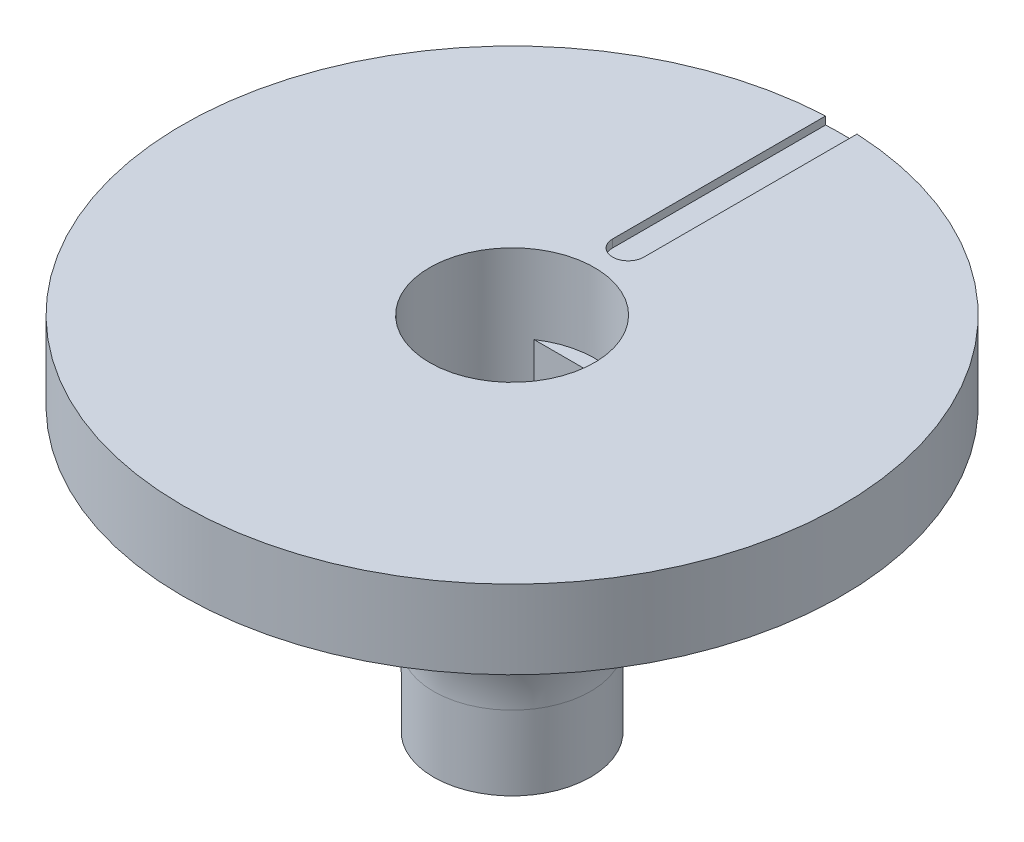
SolidWorks part; units mm, degrees
other "Markup1"
sketch "Sketch12" plane through (10.5, -11, 10.5) normal (0.0629, -0.0953, 0.9935) x (-0.9831, 0.1654, 0.0781)
material "ABS"
ref_plane "Front Plane" through (0, 0, 0) normal (0, 0, 1) x (1, 0, 0)
ref_plane "Top Plane" through (0, 0, 0) normal (0, 1, 0) x (1, 0, 0)
ref_plane "Right Plane" through (0, 0, 0) normal (1, 0, 0) x (0, 0, -1)
sketch "Sketch1" plane through (0, 0, 0) normal (0, 1, 0) x (1, 0, 0)
  circle A0 centre (0, 0) radius 8.6
  circle A1 centre (0, 0) radius 10.5
  dimension "D1" = 17.2
  dimension "D2" = 21
extrude "Boss-Extrude1" add sketch "Sketch1" against normal blind 2
ref_plane "Plane1" through (0, 0, 8.6) normal (0, 0, -1) x (-1, 0, 0)
sketch "Sketch2" plane through (0, 0, 8.6) normal (0, 0, -1) x (-1, 0, 0)
  line L0 (0.4, -1.25) -> (-0.4, -1.25)
  line L1 (0.4, -1.25) -> (0.4, 0)
  line L6 (-0.4, 0) -> (-0.4, -1.25)
  line L7 (10.5, 0) -> (-10.5, 0) construction
  line L8 (0.4, 0) -> (-0.4, 0)
  point P2 (0, -1.25)
  dimension "D1" = 1.25
  dimension "D4" = 0.8
extrude "Boss-Extrude2" add sketch "Sketch2" along normal blind 1.25
ref_plane "Plane2" through (0, 0, -8.6) normal (0, 0, 1) x (1, 0, 0)
extrude "Boss-Extrude3" add sketch "Sketch2<2>" against normal blind 1.25 from surface starting at plane "Plane2"
sketch "Sketch2<2>" plane through (0, 0, 8.6) normal (0, 0, -1) x (-1, 0, 0) same geometry as "Sketch2"
sketch "Sketch3" plane through (0, 0, 0) normal (0, 1, 0) x (1, 0, 0)
  circle A1 centre (0, 0) radius 10.5
  circle A2 centre (0, 0) radius 10.5
  dimension "D1" = 0
extrude "Boss-Extrude4" add sketch "Sketch3" along normal blind 0.5
sketch "Sketch5" plane through (0, 0, 0) normal (0, -1, 0) x (1, 0, 0)
  circle A1 centre (0, 0) radius 3.25
  dimension "D2" = 6.5
extrude "Boss-Extrude5" add sketch "Sketch5" along normal blind 6
fillet "Fillet2" radius 0.75 1 edges at (0, 0, 3.25)
sketch "Sketch4" plane through (0, 0.5, 0) normal (0, 1, 0) x (1, 0, 0)
  line L0 (-1.4697, 2.175) -> (1.4697, 2.175)
  line L1 (-3.1755, -2.625) -> (3.3726, -2.625) construction
  arc A0 (-1.4697, 2.175) -> (1.4697, 2.175) centre (0, 0) ccw
  dimension "D1" = 5.25
  dimension "D2" = 4.8
extrude "Cut-Extrude1" cut sketch "Sketch4" against normal blind 5.5
fillet "Fillet1" radius 0.25 4 edges at (-0.4, -1.25, 7.9703) (0.4, -1.25, 7.9703) (-0.4, -1.25, -7.9703) (0.4, -1.25, -7.9703)
sketch "Sketch7" plane through (0, 0.5, 0) normal (0, 1, 0) x (1, 0, 0)
  circle A2 centre (0, 0) radius 2.625
  arc A3 (-1.4697, 2.175) -> (1.4697, 2.175) centre (0, 0) ccw construction
extrude "Cut-Extrude2" cut sketch "Sketch7" against normal blind 2.5
sketch "Sketch9" plane through (0, 0.5, 0) normal (0, 1, 0) x (1, 0, 0)
  line L0 (0, 3.7) -> (0, 13.7) construction
  line L1 (-0.5, 3.7) -> (-0.5, 13.7)
  line L2 (0.5, 3.7) -> (0.5, 13.7)
  arc A0 (-0.5, 3.7) -> (0.5, 3.7) centre (0, 3.7) ccw
  arc A1 (0.5, 13.7) -> (-0.5, 13.7) centre (0, 13.7) ccw
  point P3 (0, 8.7)
  dimension "D1" = 1
  dimension "D2" = 10
  dimension "D3" = 3.7
extrude "Cut-Extrude3" cut sketch "Sketch9" against normal blind 0.25
sketch "Sketch11" plane through (0, -6, 0) normal (0, -1, 0) x (1, 0, 0)
  circle A0 centre (0, 0) radius 2.5
  dimension "D1" = 5
extrude "Boss-Extrude6" add sketch "Sketch11" along normal blind 5
sketch "Sketch10" plane through (0, -6, 0) normal (0, -1, 0) x (1, 0, 0)
  line L1 (1.8042, 0) -> (0.9021, 1.5625)
  line L2 (0.9021, 1.5625) -> (-0.9021, 1.5625)
  line L3 (-0.9021, 1.5625) -> (-1.8042, 0)
  line L4 (-1.8042, 0) -> (-0.9021, -1.5625)
  line L5 (-0.9021, -1.5625) -> (0.9021, -1.5625)
  line L6 (0.9021, -1.5625) -> (1.8042, 0)
  circle A0 centre (0, 0) radius 1.5625 construction
  dimension "D1" = 3.125
extrude "Cut-Extrude4" cut sketch "Sketch10" against normal blind 4.5 from surface starting at face at (0, -11, -2.5)
chamfer "Chamfer2" distance 0.25 angle 45 6 edges at (-1.3532, -11, 0.7813) (-1.3532, -11, -0.7813) (0, -11, -1.5625) (1.3532, -11, -0.7813) (1.3532, -11, 0.7813) (0, -11, 1.5625)
fillet "Fillet3" radius 5 1 edges at (0, -6, -2.5)
ref_axis "Axis1" through (0, 1.075, 0) along (0, -1, 0)
